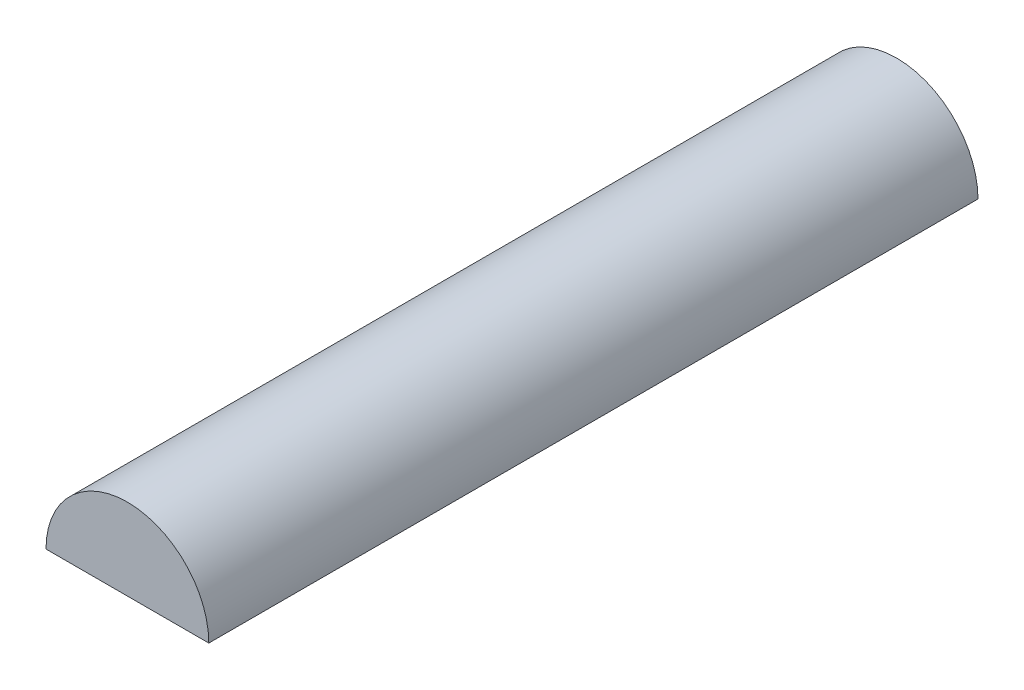
SolidWorks part; units mm, degrees
material "6061-T6 (SS)"
ref_plane "Front Plane" through (0, 0, 0) normal (0, 0, 1) x (1, 0, 0)
ref_plane "Top Plane" through (0, 0, 0) normal (0, 1, 0) x (1, 0, 0)
ref_plane "Right Plane" through (0, 0, 0) normal (1, 0, 0) x (0, 0, -1)
sketch "Sketch1" plane through (0, 0, 0) normal (0, 0, 1) x (1, 0, 0)
  line L0 (-1.5875, 0) -> (1.5875, 0)
  arc A0 (-1.5875, 0) -> (1.5875, 0) centre (0, 0) cw
  dimension "D1" = 1.5875
extrude "Boss-Extrude1" add sketch "Sketch1" along normal blind 15
equation "\"D1@Boss-Extrude1\"=15mm"
